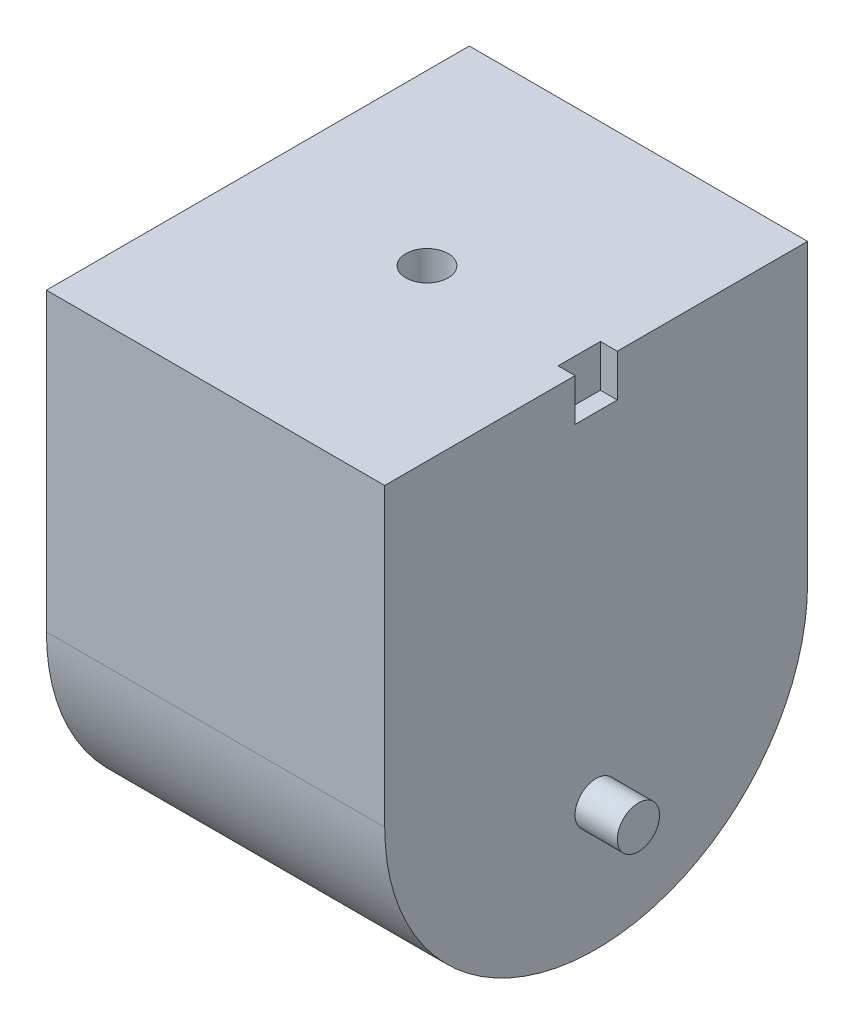
SolidWorks part; units mm, degrees
ref_plane "Front Plane" through (0, 0, 0) normal (0, 0, 1) x (1, 0, 0)
ref_plane "Top Plane" through (0, 0, 0) normal (0, 1, 0) x (1, 0, 0)
ref_plane "Right Plane" through (0, 0, 0) normal (1, 0, 0) x (0, 0, -1)
sketch "Sketch1" plane through (0, 0, 0) normal (0, 0, 1) x (1, 0, 0)
  line L1 (0, 0) -> (50.8, 0)
  line L2 (0, 0) -> (0, 76.2)
  line L3 (0, 76.2) -> (50.8, 76.2)
  line L4 (50.8, 0) -> (50.8, 76.2)
  dimension "D1" = 50.8
  dimension "D2" = 76.2
extrude "Boss-Extrude1" add sketch "Sketch1" along normal blind 63.5
fillet "Fillet2" 2 edges at (25.4, 0, 0) (25.4, 0, 63.5) type full round first side face at (25.4, 38.1, 0) second side face at (25.4, 38.1, 63.5) middle face at (25.4, 0, 31.75)
sketch "Sketch2" plane through (50.8, 0, 0) normal (1, 0, 0) x (0, 0, -1)
  line L0 (-63.5, 31.75) -> (0, 31.75) construction
  circle A0 centre (-31.75, 19.05) radius 3.175
  point P6 (-18.2253, 8.89)
  point P7 (-31.75, 31.75)
  dimension "D2" = 6.35
  dimension "D1" = 12.7
extrude "Boss-Extrude2" add sketch "Sketch2" along normal blind 6.35
ref_plane "Plane1" through (25.4, 0, 0) normal (1, 0, 0) x (0, 0, -1)
ref_plane "Plane2" through (0, 0, 31.75) normal (0, 0, 1) x (1, 0, 0)
mirror "Mirror1" about plane through (25.4, 0, 0) normal (1, 0, 0) of "Boss-Extrude2"
sketch "Sketch3" plane through (0, 76.2, 0) normal (0, 1, 0) x (1, 0, 0)
  line L0 (25.4, -34.925) -> (25.4, 34.925) construction
  line L1 (-27.94, -31.75) -> (27.94, -31.75) construction
  circle A0 centre (25.4, -31.75) radius 3.175
  point P6 (16.51, -16.51)
  dimension "D1" = 6.35
extrude "Cut-Extrude1" cut sketch "Sketch3" against normal blind 6.35
sketch "Sketch4" plane through (50.8, 0, 0) normal (1, 0, 0) x (0, 0, -1)
  line L0 (-63.5, 76.2) -> (0, 76.2) construction
  line L1 (-28.575, 76.2) -> (-34.925, 76.2)
  line L2 (-28.575, 76.2) -> (-28.575, 69.85)
  line L3 (-28.575, 69.85) -> (-34.925, 69.85)
  line L4 (-34.925, 76.2) -> (-34.925, 69.85)
  line L6 (-31.75, 76.2) -> (-31.75, 54.3342) construction
  dimension "D2" = 6.35
  dimension "D3" = 6.35
extrude "Cut-Extrude2" cut sketch "Sketch4" against normal blind 2.54
